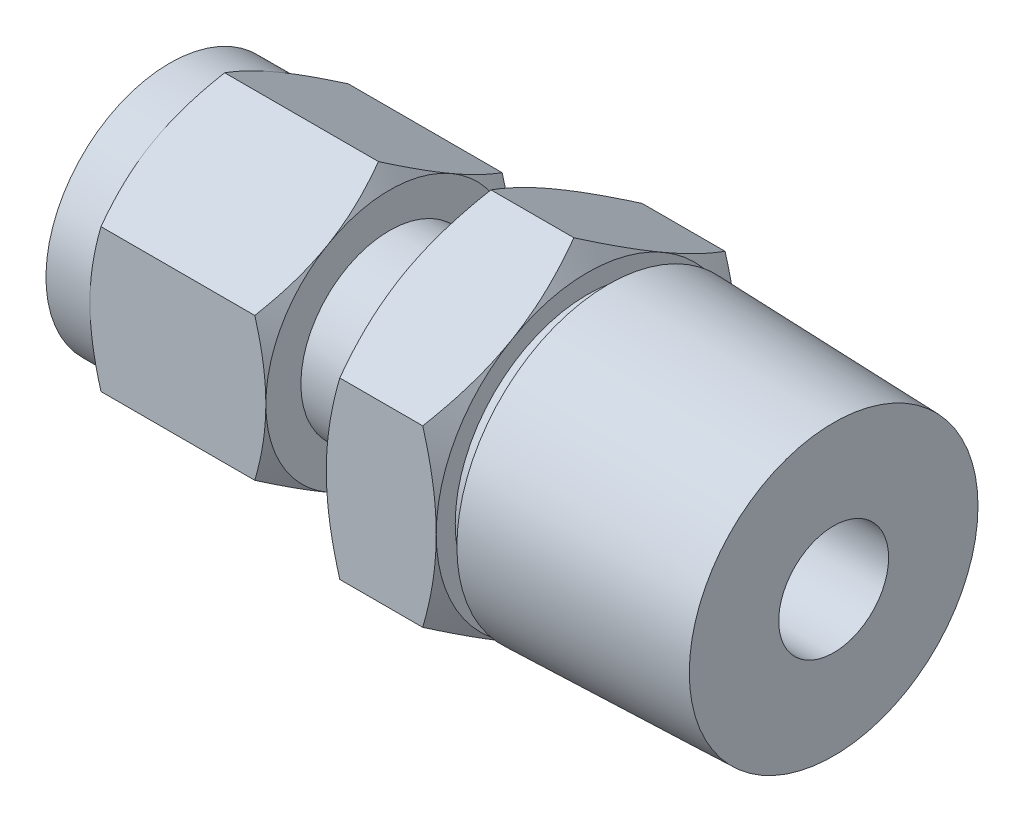
SolidWorks part; units mm, degrees
material "Brass"
ref_plane "Front Plane" through (0, 0, 0) normal (0, 0, 1) x (1, 0, 0)
ref_plane "Top Plane" through (0, 0, 0) normal (0, 1, 0) x (1, 0, 0)
ref_plane "Right Plane" through (0, 0, 0) normal (1, 0, 0) x (0, 0, -1)
other "Configuration Table"
sketch "Sketch5" plane through (0, 0, 0) normal (0, 0, 1) x (1, 0, 0)
  line L0 (0, 0) -> (-7.7637, 0) construction
  line L1 (-7.3838, -3.175) -> (-7.3838, -2.921)
  line L2 (-7.3838, -2.921) -> (-14.224, -2.921)
  line L5 (-13.02, -8.7427) -> (0, -8.3381)
  line L6 (0, -8.3381) -> (0, -3.175)
  line L8 (-13.6602, -7.634) -> (-13.02, -8.7427)
  line L10 (-14.224, -7.634) -> (-13.6602, -7.634)
  line L12 (-14.224, -2.921) -> (-14.224, -7.634)
  line L16 (0, -3.175) -> (-7.3838, -3.175)
  dimension "D2" = 0.254
  dimension "pipe-a" = 13.02
  dimension "pipe-b" = 14.224
  dimension "pipe thread dia" = 17.4854
  dimension "D7" = 120
  dimension "pipe-neck down" = 15.2679
  dimension "mate ref dist" = 7.3838
revolve "Revolve1" add sketch "Sketch5" angle 360 about L0
cosmetic thread "Cosmetic Thread1" parameters "D2"=14.6721
sketch "Sketch16" plane through (-14.224, 0, 0) normal (-1, 0, 0) x (0, 0, 1)
  line L1 (0, 10.082) -> (-8.7312, 5.041)
  line L2 (-8.7312, 5.041) -> (-8.7312, -5.041)
  line L3 (-8.7312, -5.041) -> (0, -10.082)
  line L4 (0, -10.082) -> (8.7312, -5.041)
  line L5 (8.7312, -5.041) -> (8.7312, 5.041)
  line L6 (8.7312, 5.041) -> (0, 10.082)
  circle A0 centre (0, 0) radius 8.7312 construction
  circle A1 centre (0, 0) radius 2.921 construction
  circle A2 centre (0, 0) radius 2.921
  dimension "pipe hex" = 17.4625
extrude "Extrude6" add sketch "Sketch16" along normal blind 6.35
sketch "Sketch17" plane through (-20.574, 0, 0) normal (-1, 0, 0) x (0, 0, 1)
  line L0 (8.7312, 5.041) -> (0, 10.082) construction
  circle A0 centre (0, 0) radius 8.7312
extrude "Extrude7" cut sketch "Sketch17" against normal blind 6.35 draft 60 flip side to cut
sketch "Sketch18" plane through (-14.224, 0, 0) normal (1, 0, 0) x (0, 0, -1)
  line L0 (-8.7312, 5.041) -> (0, 10.082) construction
  circle A0 centre (0, 0) radius 8.7312
extrude "Extrude8" cut sketch "Sketch18" against normal blind 6.35 draft 60 flip side to cut
ref_plane "Plane2" through (-25.654, 0, 0) normal (1, 0, 0) x (0, 0, -1)
sketch "Sketch6" plane through (-25.654, 0, 0) normal (1, 0, 0) x (0, 0, -1)
  line L1 (0, -8.2489) -> (7.1437, -4.1244)
  line L2 (7.1437, -4.1244) -> (7.1438, 4.1244)
  line L3 (7.1438, 4.1244) -> (0, 8.2489)
  line L4 (0, 8.2489) -> (-7.1437, 4.1244)
  line L5 (-7.1437, 4.1244) -> (-7.1437, -4.1244)
  line L6 (-7.1437, -4.1244) -> (0, -8.2489)
  circle A0 centre (0, 0) radius 7.1438 construction
  circle A1 centre (0, 0) radius 2.921 construction
  circle A2 centre (0, 0) radius 2.921
  dimension "tube hex" = 14.2875
extrude "Extrude1" add sketch "Sketch6" against normal blind 10.16
sketch "Sketch8" plane through (-35.814, 0, 0) normal (-1, 0, 0) x (0, 0, 1)
  line L0 (0, 8.2489) -> (7.1437, 4.1244) construction
  circle A0 centre (0, 0) radius 7.1437
extrude "Extrude2" cut sketch "Sketch8" against normal blind 1.524 draft 60 flip side to cut
sketch "Sketch9" plane through (-25.654, 0, 0) normal (1, 0, 0) x (0, 0, -1)
  line L0 (0, 8.2489) -> (-7.1437, 4.1244) construction
  circle A0 centre (0, 0) radius 7.1437
extrude "Extrude3" cut sketch "Sketch9" against normal blind 6.35 draft 60 flip side to cut
sketch "Sketch11" plane through (0, 0, 0) normal (0, 0, 1) x (1, 0, 0)
  line L0 (-25.654, 2.921) -> (-35.814, 2.921) construction
  line L2 (-21.463, 4.4983) -> (-21.8897, 5.2375)
  line L3 (-14.224, 4.4983) -> (-21.463, 4.4983)
  line L4 (0, -8.3381) -> (0, 8.3381) construction
  line L5 (-21.8897, 5.2375) -> (-30.734, 4.9626)
  line L6 (-14.224, -7.634) -> (-14.224, 7.634) construction
  line L7 (-30.734, 8.2489) -> (-30.734, 7.2099) construction
  line L8 (-38.354, 2.921) -> (-14.224, 2.921)
  line L9 (-35.1759, 8.2489) -> (-26.2921, 8.2489) construction
  line L11 (-30.734, 7.1437) -> (-38.354, 7.1437)
  line L12 (-30.734, 7.1437) -> (-30.734, 4.9626)
  line L13 (-38.354, 7.1437) -> (-38.354, 2.921)
  line L14 (-14.224, 4.4983) -> (-14.224, 2.921)
  line L17 (0, 0) -> (-14.224, 0) construction
  dimension "tube-dia" = 14.2875
  dimension "OAL" = 38.354
  dimension "D6" = 120
  dimension "tube-neck down" = 8.9967
  dimension "tube-c" = 16.4643
  dimension "tube taper dia" = 10.475
revolve "Revolve2" add sketch "Sketch11" angle 360 about L17
sketch "Sketch15" plane through (-38.354, 0, 0) normal (-1, 0, 0) x (0, 0, 1)
  circle A0 centre (0, 0) radius 3.175
extrude "Extrude5" cut sketch "Sketch15" against normal blind 15.24
sketch "Sketch19" plane through (-14.224, 0, 0) normal (1, 0, 0) x (0, 0, -1)
  point P0 (0, 0)
other "RPoint1"
other "CPoint1" parameters "Diameter"=6.35, "StubLength"=23.8125
ref_axis "Axis1" through (-33.114, 0, 0) along (1, 0, 0)
ref_axis "Axis of Rotation" through (-13.02, 0, 0) along (1, 0, 0)
